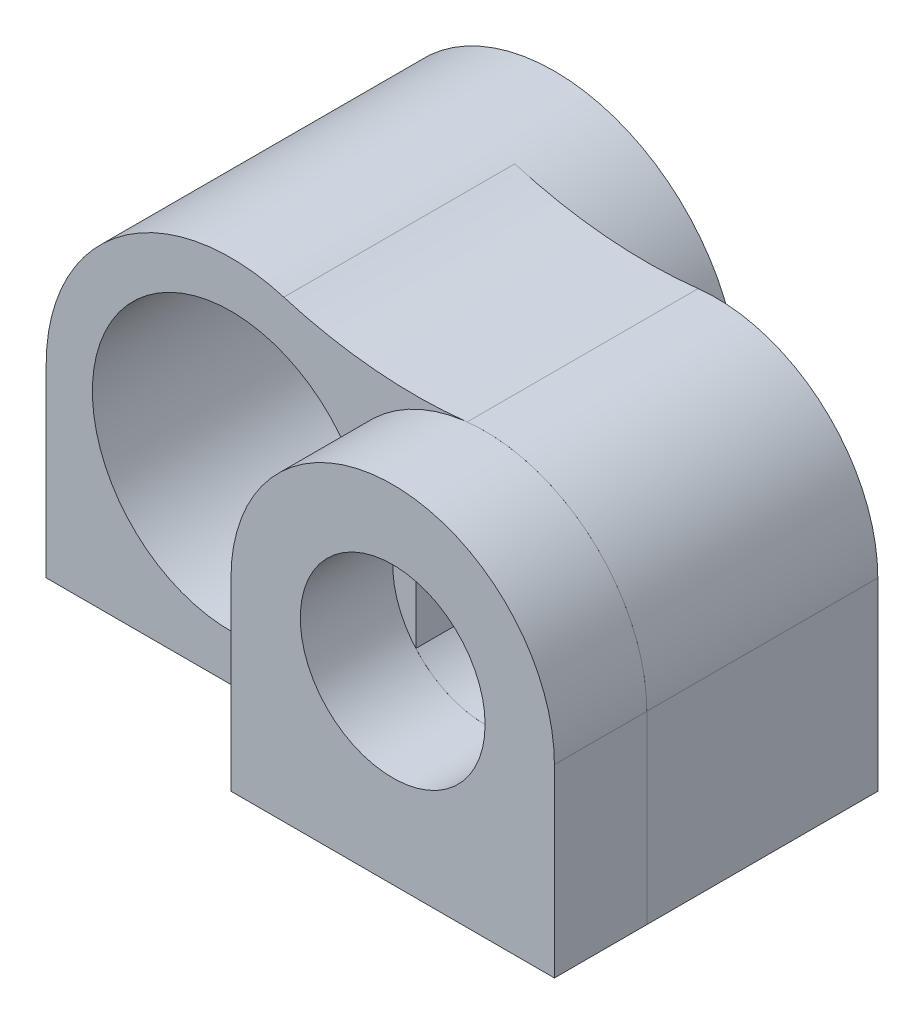
SolidWorks part; units mm, degrees
ref_plane "Front Plane" through (0, 0, 0) normal (0, 0, 1) x (1, 0, 0)
ref_plane "Top Plane" through (0, 0, 0) normal (0, 1, 0) x (1, 0, 0)
ref_plane "Right Plane" through (0, 0, 0) normal (1, 0, 0) x (0, 0, -1)
sketch "Sketch2" plane through (0, 0, 0) normal (0, 0, 1) x (1, 0, 0)
  line L0 (-4, 0) -> (-4, -4)
  line L1 (-4, -4) -> (4, -4)
  line L2 (4, -4) -> (4, 0)
  circle A0 centre (0, 0) radius 3
  arc A2 (4, 0) -> (-4, 0) centre (0, 0) ccw
  dimension "D2" = 6
  dimension "D3" = 4
  dimension "D1" = 4
extrude "Boss-Extrude1" add sketch "Sketch2" along normal blind 7
sketch "Sketch3" plane through (0, 0, 7) normal (0, 0, 1) x (1, 0, 0)
  line L0 (2, 0) -> (2, -4)
  line L1 (-4, -4) -> (4, -4) construction
  line L2 (2, -4) -> (9, -4)
  line L3 (9, -4) -> (9, 0)
  line L4 (4, -4) -> (4, 0) construction
  line L5 (4, -4) -> (4, 0)
  circle A0 centre (5.5, 0) radius 2
  arc A1 (9, 0) -> (2, 0) centre (5.5, 0) ccw
  arc A2 (4, 0) -> (-4, 0) centre (0, 0) ccw construction
  arc A3 (4, 0) -> (3.0909, 2.539) centre (0, 0) ccw
  arc M6 (4, 0) -> (-4, 0) centre (0, 0) ccw
  line M8 (-4, -4) -> (4, -4)
  line M9 (4, -4) -> (4, 0)
  circle M10 centre (0, 0) radius 3
  dimension "D1" = 4
  dimension "D2" = 7
  dimension "D3" = 5.5
extrude "Boss-Extrude2" add sketch "Sketch3" against normal blind 5 contours L3 A1 A0 L2 M6 M9 region at (6.844, 3.128, 7)
extrude "Boss-Extrude4" add sketch "Sketch3<3>" along normal blind 2 separate body contours L3 A1 A0 L2 M6 M9 | A0 L0 M10 M8 M9 | A1 L0 M10 region at (2.4432, -0.209, 7) region at (3.1149, -1.507, 7) region at (6.844, 3.128, 7)
sketch "Sketch3<3>" plane through (0, 0, 7) normal (0, 0, 1) x (1, 0, 0) same geometry as "Sketch3"
fillet "Fillet1" radius 10 1 edges at (3.0909, 2.539, 4.5)
